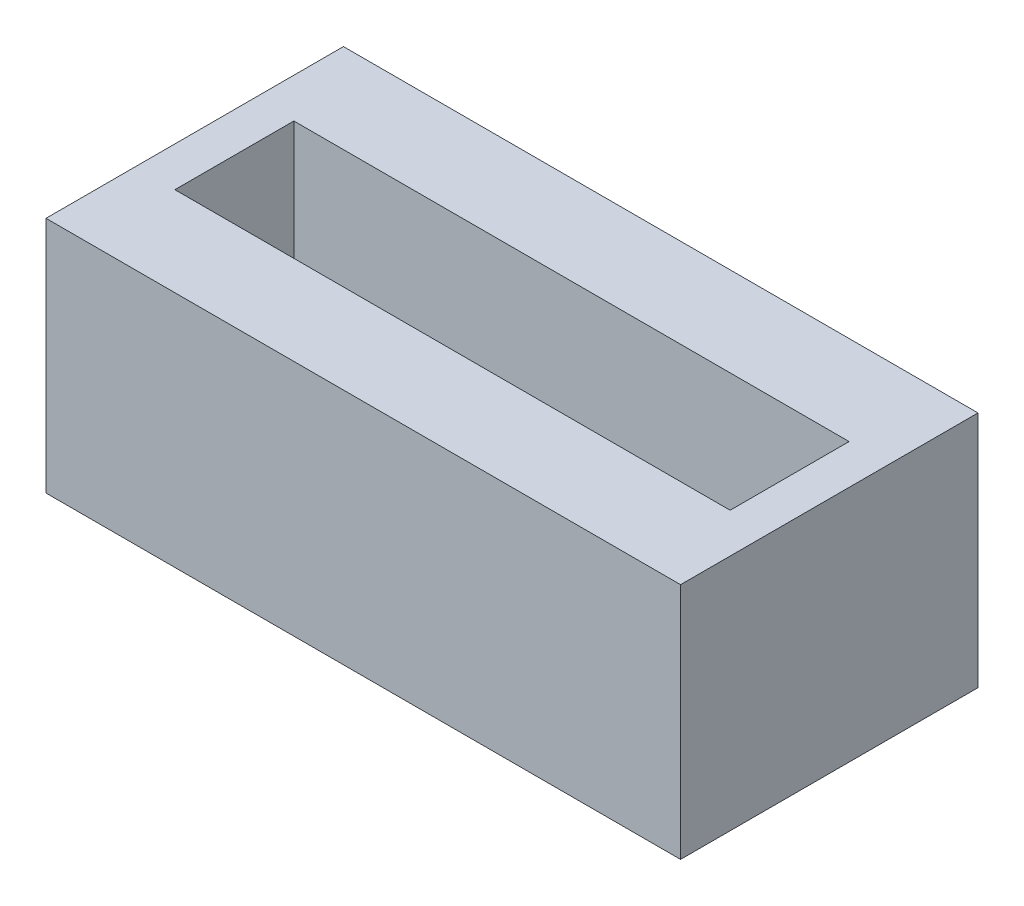
SolidWorks part; units mm, degrees
ref_plane "Front Plane" through (0, 0, 0) normal (0, 0, 1) x (1, 0, 0)
ref_plane "Top Plane" through (0, 0, 0) normal (0, 1, 0) x (1, 0, 0)
ref_plane "Right Plane" through (0, 0, 0) normal (1, 0, 0) x (0, 0, -1)
sketch "Sketch1" plane through (0, 0, 0) normal (0, 1, 0) x (1, 0, 0)
  line L1 (-14, -3) -> (14, -3)
  line L2 (-14, -3) -> (-14, 3)
  line L3 (-14, 3) -> (14, 3)
  line L4 (14, -3) -> (14, 3)
  line L5 (-14, -3) -> (14, 3) construction
  line L6 (-14, 3) -> (14, -3) construction
  line L7 (-16, -7.5) -> (16, -7.5)
  line L8 (-16, -7.5) -> (-16, 7.5)
  line L9 (-16, 7.5) -> (16, 7.5)
  line L10 (16, -7.5) -> (16, 7.5)
  line L11 (-16, -7.5) -> (16, 7.5) construction
  line L12 (-16, 7.5) -> (16, -7.5) construction
  point P0 (0, 0)
  point P6 (0, 0)
  dimension "D1" = 28
  dimension "D2" = 6
  dimension "D3" = 32
  dimension "D4" = 15
extrude "Boss-Extrude1" add sketch "Sketch1" along normal blind 12 contours L7 L10 L9 L8
extrude "Cut-Extrude1" cut sketch "Sketch1<3>" along normal blind 12 contours L1 L4 L3 L2
sketch "Sketch1<3>" plane through (0, 0, 0) normal (0, 1, 0) x (1, 0, 0) same geometry as "Sketch1"
